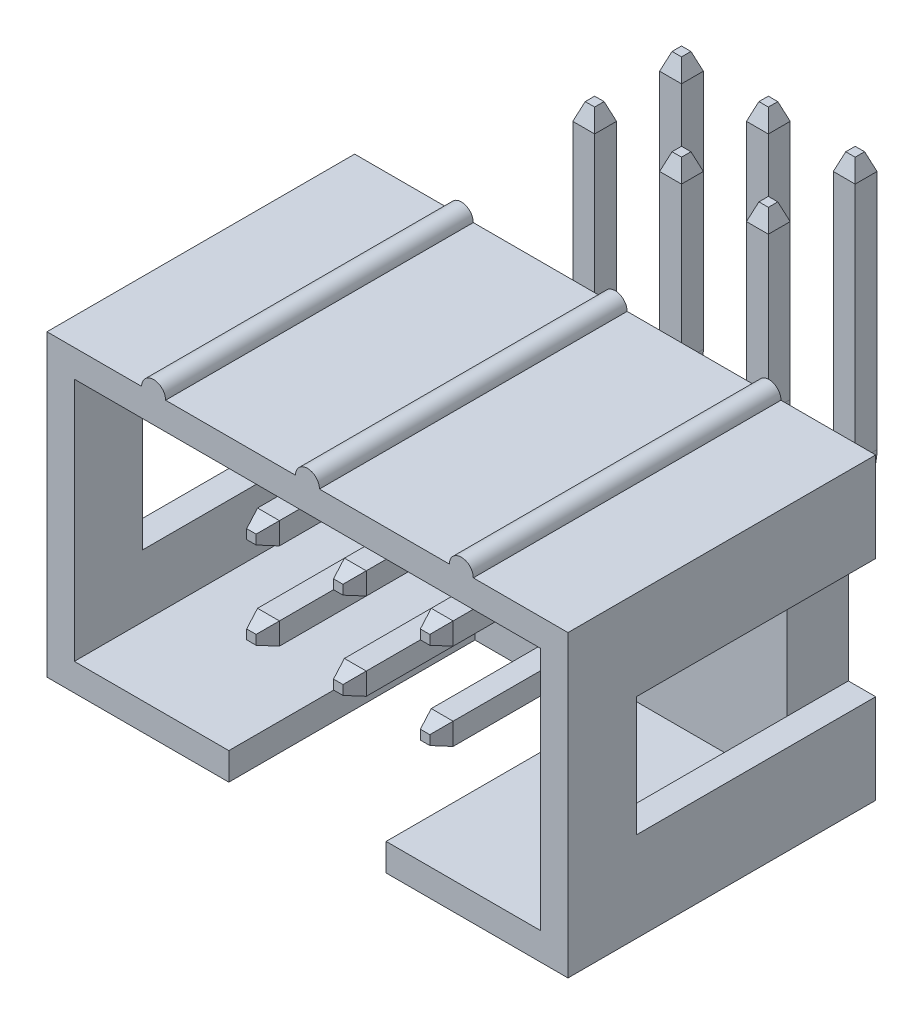
SolidWorks part; units mm, degrees
ref_plane "Спереди" through (0, 0, 0) normal (0, 0, 1) x (1, 0, 0)
ref_plane "Сверху" through (0, 0, 0) normal (0, 1, 0) x (1, 0, 0)
ref_plane "Справа" through (0, 0, 0) normal (1, 0, 0) x (0, 0, -1)
sketch "Эскиз1" plane through (0, 0, 0) normal (0, 0, 1) x (1, 0, 0)
  line L1 (-7.62, -4.375) -> (7.62, -4.375)
  line L2 (-7.62, -4.375) -> (-7.62, 4.375)
  line L3 (-7.62, 4.375) -> (7.62, 4.375)
  line L4 (7.62, -4.375) -> (7.62, 4.375)
  point P4 (0, 4.375)
  point P6 (-7.62, 0)
  dimension "D1" = 8.75
  dimension "D2" = 15.24
extrude "Бобышка-Вытянуть1" add sketch "Эскиз1" along normal blind 1.8
sketch "Эскиз2" plane through (0, 0, 1.8) normal (0, 0, 1) x (1, 0, 0)
  line L1 (-7.62, 4.375) -> (7.62, 4.375)
  line L2 (-7.62, 4.375) -> (-7.62, -4.375)
  line L3 (-7.62, -4.375) -> (7.62, -4.375)
  line L4 (7.62, 4.375) -> (7.62, -4.375)
  line L5 (-6.82, 3.575) -> (6.82, 3.575)
  line L6 (-6.82, 3.575) -> (-6.82, -3.575)
  line L7 (-6.82, -3.575) -> (6.82, -3.575)
  line L8 (6.82, 3.575) -> (6.82, -3.575)
  dimension "D1" = 0.8
  dimension "D2" = 0.8
  dimension "D3" = 0.8
  dimension "D4" = 0.8
extrude "Бобышка-Вытянуть2" add sketch "Эскиз2" along normal offset from surface (7.2 mm away) 9 up to face at (0, 0, 0)
sketch "Эскиз3" plane through (0, 0, 1.8) normal (0, 0, 1) x (1, 0, 0)
  line L0 (-7.62, 4.375) -> (-7.62, -4.375) construction
  line L1 (6.82, 1.75) -> (7.62, 1.75)
  line L2 (6.82, 1.75) -> (6.82, -1.75)
  line L3 (6.82, -1.75) -> (7.62, -1.75)
  line L4 (7.62, 1.75) -> (7.62, -1.75)
  line L5 (6.82, 1.75) -> (7.62, -1.75) construction
  line L6 (6.82, -1.75) -> (7.62, 1.75) construction
  line L7 (-6.82, 1.75) -> (-7.62, 1.75)
  line L8 (-6.82, 1.75) -> (-6.82, -1.75)
  line L9 (-6.82, -1.75) -> (-7.62, -1.75)
  line L10 (-7.62, 1.75) -> (-7.62, -1.75)
  line L11 (-6.82, 1.75) -> (-7.62, -1.75) construction
  line L12 (-6.82, -1.75) -> (-7.62, 1.75) construction
  line L13 (-6.82, 3.575) -> (-6.82, -3.575) construction
  line L14 (7.62, -4.375) -> (7.62, 4.375) construction
  line L16 (6.82, -3.575) -> (6.82, 3.575) construction
  point P0 (7.22, 0)
  point P5 (-7.22, 0)
  dimension "D1" = 3.5
extrude "Вырез-Вытянуть1" cut sketch "Эскиз3" against normal up to surface (1.8 mm away) and the other way offset from surface 2 up to face at (0, 0, 0) other way up to face at (0, 0, 9)
sketch "Эскиз4" plane through (0, 0, 9) normal (0, 0, 1) x (1, 0, 0)
  line L0 (6.82, -3.575) -> (-6.82, -3.575) construction
  line L1 (-2.3, -4.375) -> (2.3, -4.375)
  line L2 (-2.3, -4.375) -> (-2.3, -3.575)
  line L3 (-2.3, -3.575) -> (2.3, -3.575)
  line L4 (2.3, -4.375) -> (2.3, -3.575)
  line L5 (-2.3, -4.375) -> (2.3, -3.575) construction
  line L6 (-2.3, -3.575) -> (2.3, -4.375) construction
  line L7 (7.62, -4.375) -> (-7.62, -4.375) construction
  point P0 (0, -3.975)
  point P9 (0, 0)
  dimension "D1" = 4.6
extrude "Вырез-Вытянуть2" cut sketch "Эскиз4" against normal up to surface (7.2 mm away) up to face at (0, 0, 1.8)
sketch "Эскиз5" plane through (0, 0, 1.8) normal (0, 0, 1) x (1, 0, 0)
  line L0 (-2.54, 1.27) -> (2.54, 1.27) construction
  line L1 (2.54, 1.27) -> (2.54, -1.27) construction
  line L2 (2.54, -1.27) -> (-2.54, -1.27) construction
  line L3 (-2.54, -1.27) -> (-2.54, 1.27) construction
  line L5 (0, -1.27) -> (0, 1.27) construction
  line L6 (-0.32, 0.95) -> (0.32, 0.95)
  line L7 (-0.32, 0.95) -> (-0.32, 1.59)
  line L8 (-0.32, 1.59) -> (0.32, 1.59)
  line L9 (0.32, 0.95) -> (0.32, 1.59)
  line L10 (-0.32, 0.95) -> (0.32, 1.59) construction
  line L11 (-0.32, 1.59) -> (0.32, 0.95) construction
  point P11 (0, 1.27)
  dimension "D1" = 2.54
  dimension "D2" = 2.54
  dimension "D3" = 0.64
sketch "Эскиз6" plane through (0, -4.375, 0) normal (0, -1, 0) x (1, 0, 0)
  line L0 (-4.9764, 5.1897) -> (-3.1846, 5.1897)
  line L1 (-3.1846, 5.1897) -> (-4.0805, 3.7162)
  line L2 (-4.0805, 3.7162) -> (-4.9764, 5.1897)
extrude "Вырез-Вытянуть3" cut sketch "Эскиз6" against normal blind 0.1
sketch "Эскиз8" plane through (0, 0, 0) normal (0, 0, 1) x (1, 0, 0)
  line L0 (-2.54, 1.27) -> (2.54, 1.27) construction
  line L1 (2.54, 1.27) -> (2.54, -1.27) construction
  line L2 (2.54, -1.27) -> (-2.54, -1.27) construction
  line L3 (-2.54, -1.27) -> (-2.54, 1.27) construction
  line L5 (0, -1.27) -> (0, 1.27) construction
  line L6 (-0.32, -1.59) -> (0.32, -1.59)
  line L7 (-0.32, -1.59) -> (-0.32, -0.95)
  line L8 (-0.32, -0.95) -> (0.32, -0.95)
  line L9 (0.32, -1.59) -> (0.32, -0.95)
  line L10 (-0.32, -1.59) -> (0.32, -0.95) construction
  line L11 (-0.32, -0.95) -> (0.32, -1.59) construction
  point P11 (0, -1.27)
  point P13 (0, 0)
  dimension "D1" = 2.54
  dimension "D2" = 2.54
  dimension "D3" = 0.64
  dimension "D4" = 1.27
sketch "Эскиз9" plane through (0, 0, 0) normal (-1, 0, 0) x (0, 0, 1)
  line L0 (8.1, -1.27) -> (0, -1.27)
  line L1 (0, -1.27) -> (-3.48, -1.27)
  line L2 (-4.48, -0.27) -> (-4.48, 7.275)
  line L4 (9, 4.375) -> (9, -4.375) construction
  line L5 (9, 4.375) -> (0, 4.375) construction
  arc A0 (-3.48, -1.27) -> (-4.48, -0.27) centre (-3.48, -0.27) cw
  dimension "D3" = 2.9
  dimension "D4" = 1
  dimension "D1" = 0.9
  dimension "D2" = 13.48
sketch "Эскиз7" plane through (0, 0, 0) normal (1, 0, 0) x (0, 0, -1)
  line L0 (-1.8, 1.27) -> (-8.1, 1.27)
  line L1 (-1.8, -1.27) -> (-1.8, 1.27) construction
  line L2 (-1.8, 1.27) -> (0.94, 1.27)
  line L3 (1.94, 2.27) -> (1.94, 7.275)
  line L4 (-9, 4.375) -> (-9, -4.375) construction
  line L6 (4.48, -0.27) -> (4.48, 7.275) construction
  arc A0 (0.94, 1.27) -> (1.94, 2.27) centre (0.94, 2.27) ccw
  dimension "D3" = 1
  dimension "D1" = 0.9
  dimension "D2" = 2.54
sweep "По траектории2" add profiles "Эскиз8" path "Эскиз9"
sweep "По траектории3" add profiles "Эскиз5" path "Эскиз7"
chamfer "Фаска16" distance 0.5 angle 20 4 edges at (0, 7.275, -1.62) (-0.32, 7.275, -1.94) (0, 7.275, -2.26) (0.32, 7.275, -1.94) first distance on face at (0, 4.7725, -1.62) first distance on face at (-0.32, 4.7725, -1.94) first distance on face at (0, 4.7725, -2.26) first distance on face at (0.32, 4.7725, -1.94)
chamfer "Фаска17" distance 0.5 angle 20 4 edges at (0, 7.275, -4.16) (-0.32, 7.275, -4.48) (0, 7.275, -4.8) (0.32, 7.275, -4.48) first distance on face at (0, 3.5025, -4.16) first distance on face at (-0.32, 3.5025, -4.48) first distance on face at (0, 3.5025, -4.8) first distance on face at (0.32, 3.5025, -4.48)
chamfer "Фаска18" distance 0.5 angle 20 4 edges at (0, -1.59, 8.1) (-0.32, -1.27, 8.1) (0, -0.95, 8.1) (0.32, -1.27, 8.1) first distance on face at (0, -1.59, 2.31) first distance on face at (-0.32, -1.27, 2.31) first distance on face at (0, -0.95, 2.31) first distance on face at (0.32, -1.27, 2.31)
chamfer "Фаска19" distance 0.5 angle 20 4 edges at (0, 0.95, 8.1) (-0.32, 1.27, 8.1) (0, 1.59, 8.1) (0.32, 1.27, 8.1) first distance on face at (0, 0.95, 3.58) first distance on face at (-0.32, 1.27, 3.58) first distance on face at (0, 1.59, 3.58) first distance on face at (0.32, 1.27, 3.58)
pattern_linear "Линейный массив2" count 2 spacing 2.54 along (1, 0, 0) of "По траектории2", "По траектории3"
pattern_linear "Линейный массив3" count 2 spacing 2.54 along (-1, 0, 0) of bodies 115 116
sketch "Эскиз10" plane through (0, -4.625, 9) normal (0, 0, -1) x (1, 0, 0)
  line L0 (7.62, -0.25) -> (2.3, -0.25) construction
  line L1 (-7.62, -9) -> (7.62, -9) construction
  circle A0 centre (0, -9) radius 0.35
  circle A1 centre (4.5, -9) radius 0.35
  circle A2 centre (-4.5, -9) radius 0.35
  point P2 (0, 0)
  point P3 (3.589, -8.5786)
  point P8 (-0.5521, -8.5786)
  point P9 (5.4835, -0.25)
  point P10 (4.5, -9.35)
  point P11 (-0.7659, -9)
  point P15 (3.5965, -9.2728)
  point P16 (0, 0)
  point P18 (3.8061, -9.5976)
  point P19 (-5.0728, -9)
  point P20 (3.4216, -9)
  point P21 (0, 0)
  dimension "D1" = 4.5
  dimension "D2" = 4.5
  dimension "D3" = 9.1
extrude "Бобышка-Вытянуть3" add sketch "Эскиз10" along normal blind 9
equation "\"D3@Эскиз2\"=\"D2@Эскиз2\""
equation "\"D2@Эскиз2\"=\"D1@Эскиз2\""
equation "\"D4@Эскиз2\"=\"D1@Эскиз2\""
